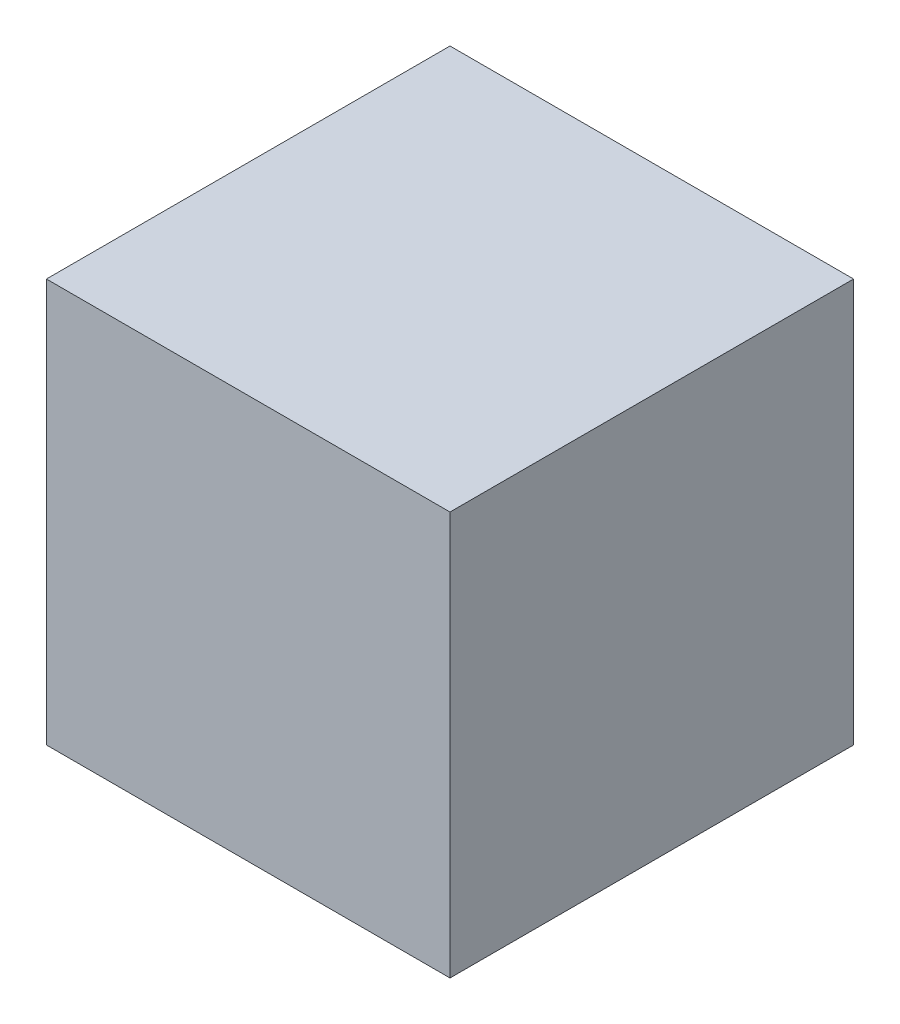
SolidWorks part; units mm, degrees
ref_plane "Front Plane" through (0, 0, 0) normal (0, 0, 1) x (1, 0, 0)
ref_plane "Top Plane" through (0, 0, 0) normal (0, 1, 0) x (1, 0, 0)
ref_plane "Right Plane" through (0, 0, 0) normal (1, 0, 0) x (0, 0, -1)
sketch "Sketch1" plane through (0, 0, 0) normal (0, 0, 1) x (1, 0, 0)
  line L1 (0.5, 0.5) -> (-0.5, 0.5)
  line L2 (0.5, 0.5) -> (0.5, -0.5)
  line L3 (0.5, -0.5) -> (-0.5, -0.5)
  line L4 (-0.5, 0.5) -> (-0.5, -0.5)
  line L5 (0.5, 0.5) -> (-0.5, -0.5) construction
  line L6 (0.5, -0.5) -> (-0.5, 0.5) construction
  point P0 (0, 0)
  dimension "D1" = 1
  dimension "D2" = 1
extrude "Boss-Extrude1" add sketch "Sketch1" along normal blind 1
equation "\"width\"= 1"
equation "\"length\"= 1"
equation "\"height\"= 1"
equation "\"D1@Sketch1\"=\"width\""
equation "\"D2@Sketch1\"=\"length\""
equation "\"D1@Boss-Extrude1\"=\"height\""
